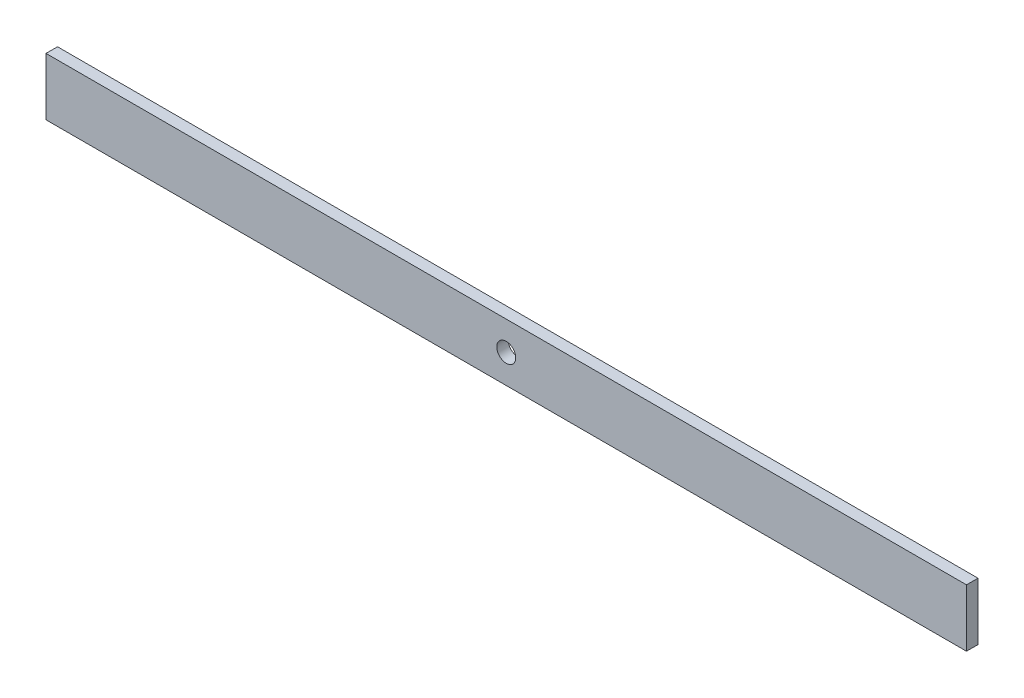
SolidWorks part; units mm, degrees
material "AISI 1020"
ref_plane "Plano frontal" through (0, 0, 0) normal (0, 0, 1) x (1, 0, 0)
ref_plane "Plano superior" through (0, 0, 0) normal (0, 1, 0) x (1, 0, 0)
ref_plane "Plano direito" through (0, 0, 0) normal (1, 0, 0) x (0, 0, -1)
sketch "Esboço1" plane through (0, 0, 0) normal (0, 0, 1) x (1, 0, 0)
  line L1 (-80, 5) -> (80, 5)
  line L2 (-80, 5) -> (-80, -5)
  line L3 (-80, -5) -> (80, -5)
  line L4 (80, 5) -> (80, -5)
  line L5 (-80, 5) -> (80, -5) construction
  line L6 (-80, -5) -> (80, 5) construction
  point P0 (0, 0)
  dimension "D1" = 160
  dimension "D2" = 10
base flange "Flange-base1" sketch "Esboço1" thickness 2 reverse thickness direction no parameters "D1"=2.7366
sketch "Esboço6" plane through (0, 0, 0) normal (0, 0, 1) x (1, 0, 0)
  line L0 (-70, 5) -> (-70, -5)
  line L1 (80, 5) -> (-80, 5) construction
  line L2 (-80, -5) -> (80, -5) construction
  line L3 (70, 5) -> (70, -5)
  line L4 (-80, 5) -> (-80, -5) construction
  dimension "D1" = 10
  dimension "D2" = 10
hole_wizard "Broca de rosquear de cano para tarraxa de 1/81" positions "Esboço7" profile "Esboço8" hole size "1/8" standard "Ansi Inch"
sketch "Esboço7" plane through (0, 0, -2) normal (0, 0, -1) x (-1, 0, 0)
  point P0 (0, 0)
sketch "Esboço8" plane through (0, 0, -2) normal (1, 0, 0) x (0, 1, 0)
  line L0 (0, 0) -> (0, 4.9914)
  line L1 (0, 4.9914) -> (1.65, 4)
  line L2 (1.65, 4) -> (1.65, 0)
  line L5 (1.65, 0) -> (0, 0)
  line L10 (0, 4.9914) -> (-1.65, 4) construction
  line L11 (0, -6.35) -> (0, 107.95) construction
  dimension "Hole Dia." = 3.3
  dimension "Hole Depth" = 4
  dimension "Drill Angle" = 118
sketch "Curva-Linhas1" [suppressed] plane through (0, 0, 0) normal (0, 1, 0) x (1, 0, 0)
sketch "Caixa delimitadora1" [suppressed] plane through (0, 0, 0) normal (0, 1, 0) x (1, 0, 0)
sheet metal parameters "Chapa metálica1" thickness 2 parameters "D1"=2.7366
flat pattern "Padrão-Plano1" [suppressed]
sketch "Curva-Linhas2" plane through (0, 0, 0) normal (0, 0, 1) x (1, 0, 0)
  line L0 (69.3562, -2.5) -> (69.3562, 2.5) construction
  line L1 (-69.3562, 2.5) -> (-69.3562, -2.5) construction
  line L2 (69.3562, -2.5) -> (69.3562, 2.5) construction
  line L3 (-69.3562, 2.5) -> (-69.3562, -2.5) construction
sketch3d "Caixa delimitadora2" [suppressed]
  line L0 (-81, -2.5, 0) -> (81, -2.5, 0) construction
  line L1 (-81, 2.5, 0) -> (81, 2.5, 0) construction
  line L2 (-81, -2.5, 0) -> (-81, 2.5, 0) construction
  line L3 (81, -2.5, 0) -> (81, 2.5, 0) construction
sheet metal parameters "Chapa metálica4" thickness 2 parameters "D1"=2.7366
flat pattern "Padrão-Plano1"
sketch "Curva-Linhas2" plane through (0, 0, 0) normal (0, 0, 1) x (1, 0, 0)
  point P0 (68.3562, -5)
  point P1 (68.3562, 5)
  point P2 (-68.3562, 5)
  point P3 (-68.3562, -5)
sketch3d "Caixa delimitadora2" [suppressed]
  line L0 (-80, -5, 0) -> (80, -5, 0) construction
  line L1 (-80, 5, 0) -> (80, 5, 0) construction
  line L2 (-80, -5, 0) -> (-80, 5, 0) construction
  line L3 (80, -5, 0) -> (80, 5, 0) construction
